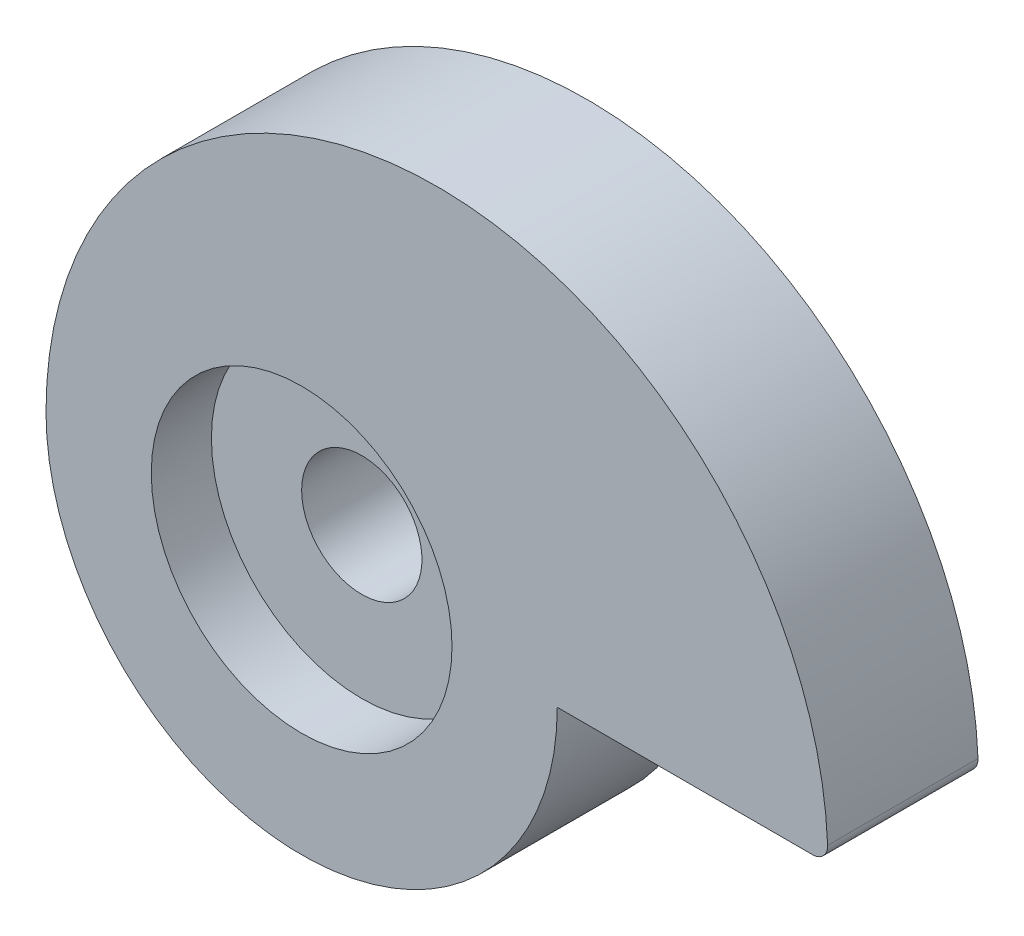
SolidWorks part; units mm, degrees
ref_plane "Front Plane" through (0, 0, 0) normal (0, 0, 1) x (1, 0, 0)
ref_plane "Top Plane" through (0, 0, 0) normal (0, 1, 0) x (1, 0, 0)
ref_plane "Right Plane" through (0, 0, 0) normal (1, 0, 0) x (0, 0, -1)
sketch "Sketch1" plane through (0, 0, 0) normal (0, 0, 1) x (1, 0, 0)
  line L0 (-13, 0) -> (13, 0) construction
  line L2 (4, 0) -> (13, 0)
  arc A0 (13, 0) -> (-13, 0) centre (0, 0) ccw
  circle A3 centre (-4.5, 0) radius 2
  arc A4 (-13, 0) -> (4, 0) centre (-4.5, 0) ccw
  dimension "D1" = 26
  dimension "D2" = 4
  dimension "D3" = 8.5
extrude "Boss-Extrude1" add sketch "Sketch1" along normal blind 5
sketch "Sketch3" plane through (0, 0, 0) normal (0, 0, 1) x (1, 0, 0)
  circle A0 centre (-4.5, 0) radius 5
  circle A1 centre (-4.5, 0) radius 2 construction
  circle A2 centre (-4.5, 0) radius 2
  dimension "D1" = 10
extrude "Boss-Extrude2" add sketch "Sketch3" against normal blind 5
sketch "Sketch4" plane through (0, 0, -5) normal (0, 0, -1) x (-1, 0, 0)
  line L1 (-2.0014, -1) -> (11.0014, -1)
  line L2 (-2.0014, -1) -> (-2.0014, 1)
  line L3 (-2.0014, 1) -> (11.0014, 1)
  line L4 (11.0014, -1) -> (11.0014, 1)
  line L5 (-2.0014, -1) -> (11.0014, 1) construction
  line L6 (-2.0014, 1) -> (11.0014, -1) construction
  point P0 (4.5, 0)
  dimension "D1" = 2
extrude "Cut-Extrude1" cut sketch "Sketch4" against normal blind 3
fillet "Fillet1" radius 1 4 edges at (-7.8155, 1, -2) (-7.8155, -1, -2) (-1.1845, -1, -2) (-1.1845, 1, -2)
sketch "Sketch5" plane through (0, 0, 5) normal (0, 0, -1) x (-1, 0, 0)
  circle A1 centre (4.5, 0) radius 5
  circle A2 centre (4.5, 0) radius 2 construction
  dimension "D1" = 10
extrude "Cut-Extrude2" cut sketch "Sketch5" along normal blind 2
fillet "Fillet2" radius 1.5 1 edges at (0.5, 0, 0)
fillet "Fillet3" radius 0.5 1 edges at (13, 0, 2.5)
